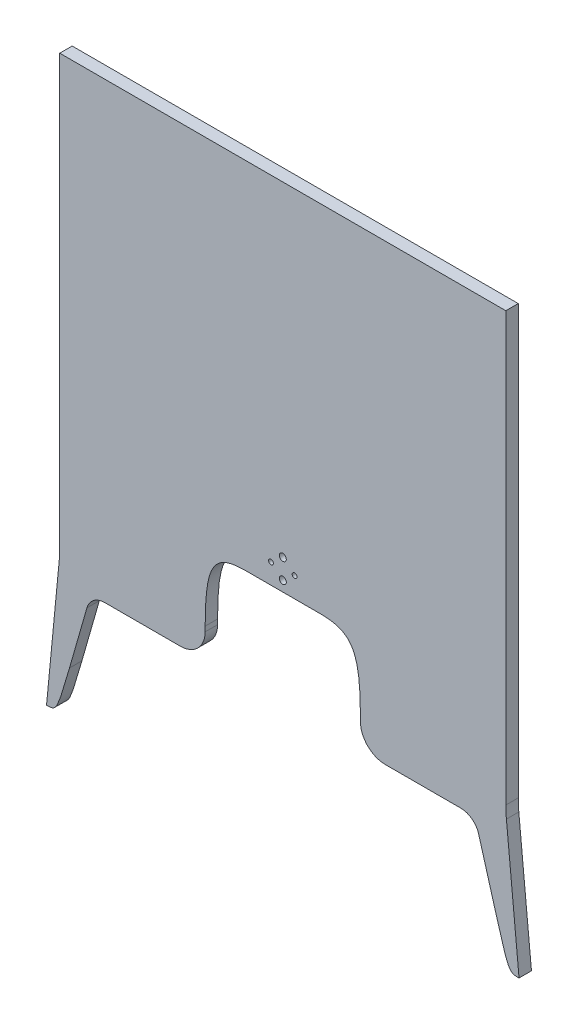
SolidWorks part; units mm, degrees
material "MDF"
ref_plane "Front Plane" through (0, 0, 0) normal (0, 0, 1) x (1, 0, 0)
ref_plane "Top Plane" through (0, 0, 0) normal (0, 1, 0) x (1, 0, 0)
ref_plane "Right Plane" through (0, 0, 0) normal (1, 0, 0) x (0, 0, -1)
sketch "Sketch1" plane through (0, 0, 0) normal (0, 0, 1) x (1, 0, 0)
  line L0 (-228.0888, 0) -> (228.0888, 0)
  line L1 (79.375, -363.22) -> (-79.375, -363.22)
  line L2 (0, -363.22) -> (0, 0) construction
  line L3 (-79.375, -363.22) -> (-79.375, -463.55)
  line L4 (196.3388, -463.55) -> (79.375, -463.55)
  line L5 (-230.9346, -584.2) -> (-196.3388, -463.55)
  line L6 (-230.9346, -584.2) -> (-241.6001, -584.2)
  line L7 (-241.6001, -584.2) -> (-228.0888, -443.879)
  line L8 (-228.0888, -443.879) -> (-228.0888, 0)
  line L9 (-196.3388, -463.55) -> (-79.375, -463.55)
  line L10 (228.0888, -443.879) -> (228.0888, 0)
  line L11 (241.6001, -584.2) -> (228.0888, -443.879)
  line L12 (230.9346, -584.2) -> (241.6001, -584.2)
  line L13 (230.9346, -584.2) -> (196.3388, -463.55)
  line L14 (79.375, -363.22) -> (79.375, -463.55)
  dimension "D1" = 363.22
  dimension "D2" = 158.75
  dimension "D3" = 106
  dimension "D4" = 31.75
  dimension "D5" = 120.65
  dimension "D6" = 174.5
  dimension "D7" = 463.55
  dimension "D8" = 140.97
extrude "Boss-Extrude1" add sketch "Sketch1" along normal blind 12.7
fillet "Fillet2" radius 69.85 1 edges at (-79.375, -363.22, 6.35) second distance 41.275 conic rho 0.6 first distance on face at (-79.375, -413.385, 6.35)
fillet "Fillet3" radius 25.4 1 edges at (-79.375, -463.55, 6.35)
fillet "Fillet4" radius 19.05 1 edges at (-196.3388, -463.55, 6.35)
ref_plane "Plane1" through (-230.9346, -584.2, 0) normal (0, 0, -1) x (-1, 0, 0)
fillet "Fillet5" radius 22.225 1 edges at (-230.9346, -584.2, 6.35) second distance 50.8 conic rho 0.7 first distance on face at (-236.2674, -584.2, 6.35)
fillet "Fillet6" radius 127 1 edges at (-228.0888, -443.879, 6.35)
sketch "Sketch3" plane through (0, 0, 12.7) normal (0, 0, 1) x (1, 0, 0)
  line L0 (0, 0) -> (0, -440.5951) construction
  line L2 (228.0888, 0) -> (-228.0888, 0) construction
  line L4 (0, 0) -> (241.6001, 0)
  line L5 (0, 0) -> (0, -584.2)
  line L6 (0, -584.2) -> (241.6001, -584.2)
  line L7 (241.6001, 0) -> (241.6001, -584.2)
  point P3 (0, 0)
extrude "Cut-Extrude1" cut sketch "Sketch3" against normal up to next
mirror "Mirror5" about plane through (0, 0, -0.3502) normal (-1, 0, 0) of bodies 103
hole_wizard "1/4 Clearance Hole1" positions "Sketch6" profile "Sketch7" hole size "1/4" standard "ANSI Inch" end condition up to next
sketch "Sketch6" plane through (0, 0, 12.7) normal (0, 0, 1) x (1, 0, 0)
  circle A0 centre (0, -352.7425) radius 4.8412 construction
  circle A1 centre (0, -332.4225) radius 4.8412 construction
  point P0 (0, -332.4225)
  point P2 (0, -352.7425)
  point P5 (-42.9344, -334.6706)
  point P8 (0, 0)
sketch "Sketch7" plane through (0, -332.4225, 12.7) normal (1, 0, 0) x (0, -1, 0)
  line L0 (0, 0) -> (0, 12.7)
  line L1 (0, 12.7) -> (3.5712, 12.7)
  line L2 (3.5712, 12.7) -> (3.5712, 0)
  line L5 (3.5712, 0) -> (0, 0)
  line L11 (0, -6.35) -> (0, 107.95) construction
  dimension "Thru Hole Dia." = 7.1425
  dimension "Thru Hole Depth" = 12.7
hole_wizard "#8 Clearance Hole1" positions "Sketch8" profile "Sketch9" hole size "#8" standard "ANSI Inch" end condition up to next
sketch "Sketch8" plane through (0, 0, 12.7) normal (0, 0, 1) x (1, 0, 0)
  arc A0 (11.4694, -341.1379) -> (12.685, -341.1379) centre (12.0772, -342.5825) ccw construction
  arc A1 (-12.9267, -341.2655) -> (-11.7296, -341.0543) centre (-12.0772, -342.5825) ccw construction
  point P0 (-12.0772, -342.5825)
  point P2 (12.0772, -342.5825)
  point P5 (11.3785, -350.6041)
  point P9 (0, 0)
sketch "Sketch9" plane through (-12.0772, -342.5825, 12.7) normal (1, 0, 0) x (0, -1, 0)
  line L0 (0, 0) -> (0, 12.7)
  line L1 (0, 12.7) -> (2.4574, 12.7)
  line L2 (2.4574, 12.7) -> (2.4574, 0)
  line L5 (2.4574, 0) -> (0, 0)
  line L11 (0, -6.35) -> (0, 107.95) construction
  dimension "Thru Hole Dia." = 4.9149
  dimension "Thru Hole Depth" = 12.7
